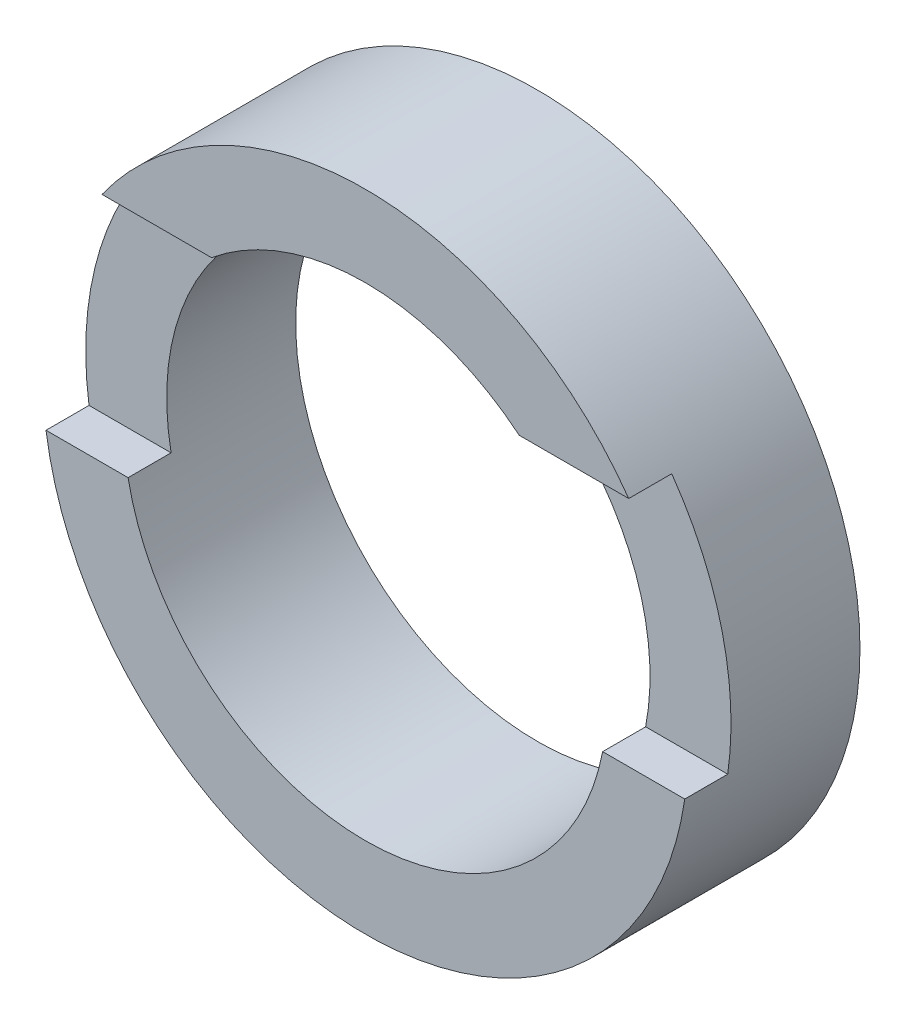
SolidWorks part; units mm, degrees
ref_plane "Ebene vorne" through (0, 0, 0) normal (0, 0, 1) x (1, 0, 0)
ref_plane "Ebene oben" through (0, 0, 0) normal (0, 1, 0) x (1, 0, 0)
ref_plane "Ebene rechts" through (0, 0, 0) normal (1, 0, 0) x (0, 0, -1)
sketch "Skizze1" plane through (0, 0, 0) normal (0, 0, 1) x (1, 0, 0)
  circle A0 centre (0, 0) radius 37.5214
  circle A1 centre (0, 0) radius 28.1055
extrude "Aufsatz-Linear austragen1" add sketch "Skizze1" along normal blind 20
sketch "Skizze2" plane through (0, 0, 20) normal (0, 0, 1) x (1, 0, 0)
  line L1 (-49.5296, 21.6754) -> (55.4093, 21.6754)
  line L2 (-49.5296, 21.6754) -> (-49.5296, -5.3317)
  line L3 (-49.5296, -5.3317) -> (55.4093, -5.3317)
  line L4 (55.4093, 21.6754) -> (55.4093, -5.3317)
extrude "Schnitt-Linear austragen1" cut sketch "Skizze2" against normal blind 5
